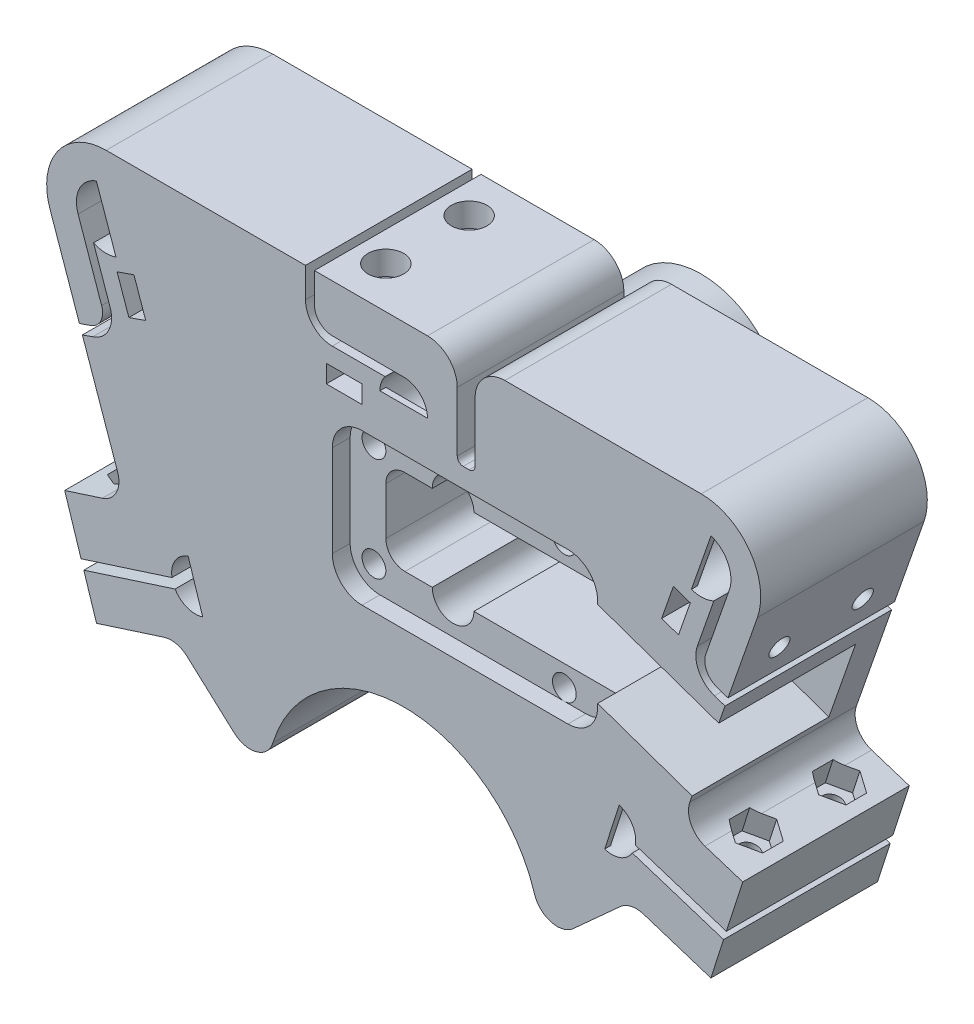
SolidWorks part; units mm, degrees
other "Uwaga1"
sketch "Szkic11" plane through (60, 10, 0) normal (0.4049, 0.0419, -0.9134) x (0.8662, -0.3375, 0.3685)
other "Uwaga2"
sketch "Szkic12" plane through (60, 10, 0) normal (0.4049, 0.0419, -0.9134) x (0.8662, -0.3375, 0.3685)
other "Uwaga3"
sketch "Szkic13"
other "Uwaga4"
sketch "Szkic23" plane through (60, 10, 28) normal (0.2859, 0.0316, 0.9577) x (0.9579, -0.038, -0.2847)
ref_plane "Płaszczyzna przednia" through (0, 0, 0) normal (0, 0, 1) x (1, 0, 0)
ref_plane "Płaszczyzna górna" through (0, 0, 0) normal (0, 1, 0) x (1, 0, 0)
ref_plane "Płaszczyzna prawa" through (0, 0, 0) normal (1, 0, 0) x (0, 0, -1)
sketch "Szkic1" plane through (0, 0, 0) normal (0, 0, 1) x (1, 0, 0)
  line L0 (-50, 10) -> (4, 10)
  line L1 (-59.4412, -3.296) -> (-43.4971, -48.9664)
  line L2 (43.4971, -48.9664) -> (59.4412, -3.296)
  line L3 (-41.0394, -52.6727) -> (-23, -69)
  line L4 (23, -69) -> (41.0394, -52.6727)
  line L5 (38.4257, -48.0651) -> (43.2433, -49.6122)
  line L6 (38.9457, -46.6566) -> (43.7633, -48.2037)
  line L7 (0, -34.7604) -> (35, -46) construction
  line L8 (38.1168, -55.318) -> (51.621, -59.6546)
  line L9 (51.621, -59.6546) -> (53.7613, -52.9898)
  line L10 (53.7613, -52.9898) -> (43.2433, -49.6122)
  line L11 (43.7633, -48.2037) -> (54.2199, -51.5616)
  line L12 (54.2199, -51.5616) -> (56.9717, -42.9926)
  line L13 (56.9717, -42.9926) -> (46.7307, -39.704)
  line L14 (0, -29) -> (0, -114.3862) construction
  line L15 (0, 2) -> (-12, 2)
  line L16 (-3.1225, 0.5) -> (-12, 0.5)
  line L17 (-16.5, 5) -> (-16.5, 10)
  line L18 (-15, 5) -> (-15, 10)
  line L19 (9, 5) -> (9, -5)
  line L20 (10, -6) -> (11, -6)
  line L21 (12, -5) -> (12, 5)
  line L22 (17, 10) -> (50, 10)
  line L23 (-56.9717, -42.9926) -> (-46.7307, -39.704)
  line L24 (-54.2199, -51.5616) -> (-56.9717, -42.9926)
  line L25 (-43.7633, -48.2037) -> (-54.2199, -51.5616)
  line L26 (-38.9457, -46.6566) -> (-43.7633, -48.2037)
  line L27 (-38.4257, -48.0651) -> (-43.2433, -49.6122)
  line L28 (-53.7613, -52.9898) -> (-43.2433, -49.6122)
  line L29 (-51.621, -59.6546) -> (-53.7613, -52.9898)
  line L30 (-38.1168, -55.318) -> (-51.621, -59.6546)
  line L31 (-54.7206, -1.648) -> (-50.7653, -12.9775)
  line L32 (-52.1248, -4.5261) -> (-49.3471, -12.4823)
  line L33 (-52.6089, -16.7986) -> (-54.4971, -17.4578)
  line L34 (-52.2456, -18.2606) -> (-54.0027, -18.874)
  line L35 (54.7206, -1.648) -> (50.7653, -12.9775)
  line L36 (52.1248, -4.5261) -> (49.3471, -12.4823)
  line L37 (52.6089, -16.7986) -> (54.4971, -17.4578)
  line L38 (52.2456, -18.2606) -> (54.0027, -18.874)
  circle A0 centre (-50, 0) radius 5
  circle A1 centre (50, 0) radius 5
  circle A2 centre (-50, 0) radius 10
  circle A3 centre (50, 0) radius 10
  circle A4 centre (0, -2) radius 4
  circle A5 centre (0, -29) radius 15.5 construction
  circle A6 centre (0, -22) radius 4
  circle A13 centre (-35, -46) radius 4
  circle A14 centre (35, -46) radius 4
  circle A15 centre (-35, -46) radius 9
  circle A16 centre (35, -46) radius 9
  arc A17 (23, -69) -> (-23, -69) centre (0, -69) ccw
  arc A19 (-12, 2) -> (-15, 5) centre (-12, 5) cw
  arc A20 (-12, 0.5) -> (-16.5, 5) centre (-12, 5) cw
  arc A21 (9, 5) -> (4, 10) centre (4, 5) ccw
  arc A22 (12, 5) -> (17, 10) centre (17, 5) cw
  arc A23 (11, -6) -> (12, -5) centre (11, -5) ccw
  arc A24 (9, -5) -> (10, -6) centre (10, -5) ccw
  arc A25 (-50.7653, -12.9775) -> (-52.6089, -16.7986) centre (-53.5977, -13.9663) cw
  arc A26 (-49.3471, -12.4823) -> (-52.2456, -18.2606) centre (-53.5977, -13.9663) cw
  arc A27 (49.3471, -12.4823) -> (52.2456, -18.2606) centre (53.5977, -13.9663) ccw
  arc A28 (50.7653, -12.9775) -> (52.6089, -16.7986) centre (53.5977, -13.9663) ccw
  point P32 (0, -29)
  point P78 (10.1421, 10)
  point P84 (10.1421, -2)
  point P87 (7.1421, -2)
  point P103 (-49.7765, -15.8098)
  dimension "D1" = 10
  dimension "D6" = 8
  dimension "D8" = 31
  dimension "D9" = 8
  dimension "D14" = 70
  dimension "D18" = 46
  dimension "D27" = 3
  dimension "D28" = 4.5
  dimension "D31" = 5
  dimension "D32" = 5
  dimension "D33" = 1
  dimension "D38" = 3
  dimension "D39" = 12.7604
  dimension "D2" = 100
  dimension "D3" = 50
  dimension "D7" = 39
  dimension "D10" = 7
  dimension "D11" = 12
  dimension "D15" = 35
  dimension "D16" = 46
  dimension "D19" = 40
  dimension "D20" = 1.5
  dimension "D21" = 7
  dimension "D22" = 20
  dimension "D23" = 9
  dimension "D24" = 1.5
  dimension "D25" = 1.5
  dimension "D26" = 15
  dimension "D29" = 3
  dimension "D30" = 16
  dimension "D34" = 9
  dimension "D35" = 15
  dimension "D36" = 1.5021
  dimension "D37" = 1.5
  dimension "D4" = 5
  dimension "D5" = 5
  dimension "D17" = 5
extrude "Dodanie-wyciągnięcie1" add sketch "Szkic1" along normal blind 28 contours A2 A0 | A17 L4 A16 L2 A3 L0 A2 L1 A15 L3 A6 A4 | A3 A1 | A16 A14 | A15 A13 | A16 L4 L8 L9 L10 | L12 L13 L2 L11 | A15 L28 L29 L30 L3 | L25 L1 L23 L24 | A25 L31 A2 L1 L33 | L35 A28 L37 L2 A3 region at (-33.25, 8.6619, 0) region at (-43.1289, 6.8711, 0) region at (-54.1165, -12.2056, 0) region at (-50.4165, -45.6303, 0) region at (-36.0734, -37.3207, 0) region at (-46.741, -54.5771, 0) region at (56.8711, 6.8711, 0) region at (46.741, -54.5771, 0) region at (54.1165, -12.2056, 0) region at (27.0061, -42.4532, 0) region at (50.4165, -45.6303, 0)
fillet "Zaokrąglenie1" radius 4 6 edges at (-46.7307, -39.704, 14) (-38.1168, -55.318, 14) (-23, -69, 14) (23, -69, 14) (38.1168, -55.318, 14) (46.7307, -39.704, 14)
sketch "Szkic2" plane through (12.5403, -39.0504, 0) normal (0.3058, -0.9521, 0) x (0.9521, 0.3058, 0)
  line L0 (-55.5122, 28) -> (-67.3885, 28) construction
  line L1 (-67.3885, 28) -> (-67.3885, 0) construction
  circle A0 centre (-62.3885, 21) radius 1.7
  circle A1 centre (-62.3885, 7) radius 1.7
  dimension "D1" = 14
  dimension "D4" = 3.4
  dimension "D2" = 7
  dimension "D3" = 5
extrude "Wytnij-wyciągnięcie1" cut sketch "Szkic2" against normal through all
sketch "Szkic3" plane through (12.5403, -39.0504, 0) normal (0.3058, -0.9521, 0) x (0.9521, 0.3058, 0)
  circle A0 centre (-62.3885, 21) radius 3
  circle A1 centre (-62.3885, 7) radius 3
  dimension "D1" = 6
extrude "Wytnij-wyciągnięcie2" cut sketch "Szkic3" against normal blind 3
sketch "Szkic4" plane through (7.1896, -22.3885, 0) normal (-0.3058, 0.9521, 0) x (0.9521, 0.3058, 0)
  line L1 (-62.3885, -24.4641) -> (-59.3885, -22.7321)
  line L2 (-59.3885, -22.7321) -> (-59.3885, -19.2679)
  line L3 (-59.3885, -19.2679) -> (-62.3885, -17.5359)
  line L4 (-62.3885, -17.5359) -> (-65.3885, -19.2679)
  line L5 (-65.3885, -19.2679) -> (-65.3885, -22.7321)
  line L6 (-65.3885, -22.7321) -> (-62.3885, -24.4641)
  line L7 (-62.3885, -10.4641) -> (-59.3885, -8.7321)
  line L8 (-59.3885, -8.7321) -> (-59.3885, -5.2679)
  line L9 (-59.3885, -5.2679) -> (-62.3885, -3.5359)
  line L10 (-62.3885, -3.5359) -> (-65.3885, -5.2679)
  line L11 (-65.3885, -5.2679) -> (-65.3885, -8.7321)
  line L12 (-65.3885, -8.7321) -> (-62.3885, -10.4641)
  circle A0 centre (-62.3885, -21) radius 3 construction
  circle A1 centre (-62.3885, -7) radius 3 construction
  dimension "D1" = 6
extrude "Wytnij-wyciągnięcie3" cut sketch "Szkic4" against normal blind 4 and the other way blind 4
sketch "Szkic5" plane through (-54.0092, -18.8553, 0) normal (-0.9441, -0.3296, 0) x (0, 0, 1)
  line L0 (28, 16.4802) -> (28, 1.4802) construction
  line L1 (28, 1.4802) -> (0, 1.4802) construction
  circle A0 centre (21, 6.4802) radius 1.7
  circle A1 centre (7, 6.4802) radius 1.7
  dimension "D1" = 14
  dimension "D2" = 3.4
  dimension "D3" = 7
  dimension "D4" = 5
extrude "Wytnij-wyciągnięcie4" cut sketch "Szkic5" against normal blind 10
sketch "Szkic6" plane through (-54.0092, -18.8553, 0) normal (-0.9441, -0.3296, 0) x (0, 0, 1)
  line L0 (22.7321, 9.4802) -> (28, 9.4802)
  line L1 (24.4641, 6.4802) -> (22.7321, 9.4802)
  line L2 (22.7321, 9.4802) -> (19.2679, 9.4802)
  line L3 (19.2679, 9.4802) -> (17.5359, 6.4802)
  line L4 (17.5359, 6.4802) -> (19.2679, 3.4802)
  line L5 (19.2679, 3.4802) -> (22.7321, 3.4802)
  line L6 (22.7321, 3.4802) -> (24.4641, 6.4802)
  line L7 (10.4641, 6.4802) -> (8.7321, 9.4802)
  line L8 (8.7321, 9.4802) -> (5.2679, 9.4802)
  line L9 (5.2679, 9.4802) -> (3.5359, 6.4802)
  line L10 (3.5359, 6.4802) -> (5.2679, 3.4802)
  line L11 (5.2679, 3.4802) -> (8.7321, 3.4802)
  line L12 (8.7321, 3.4802) -> (10.4641, 6.4802)
  line L13 (28, 16.4802) -> (28, 1.4802) construction
  line L14 (28, 9.4802) -> (28, 3.4802)
  line L15 (28, 3.4802) -> (22.7321, 3.4802)
  line L16 (5.2679, 9.4802) -> (0, 9.4802)
  line L17 (0, 16.4802) -> (0, 1.4802) construction
  line L18 (0, 9.4802) -> (0, 3.4802)
  line L19 (0, 3.4802) -> (5.2679, 3.4802)
  circle A0 centre (21, 6.4802) radius 3 construction
  circle A1 centre (7, 6.4802) radius 3 construction
  circle M2 centre (21, 6.4802) radius 1.7
  circle M3 centre (7, 6.4802) radius 1.7
  line M4 (0, 16.4802) -> (0, 1.4802)
  line M6 (28, 1.4802) -> (28, 16.4802)
  dimension "D1" = 6
extrude "Wytnij-wyciągnięcie5" cut sketch "Szkic6" against normal blind 3 from offset 9.5 contours L5 L6 L1 L2 L3 L4 M2 | L15 L0 L1 L6 M6 | L19 L10 L9 L16 M4 | L11 L12 L7 L8 L9 L10 M3 | M2 | M3 region at (-56.1452, -12.7372, 25.7706) region at (-56.6245, -11.3643, 23.5187) region at (-55.6658, -14.1101, 9.5187) region at (-56.1452, -12.7372, 2.2294) region at (-56.1452, -12.7372, 21) region at (-56.1452, -12.7372, 7) offset against normal yes
mirror "Lustro1" about plane through (0, 0, 0) normal (1, 0, 0) of "Wytnij-wyciągnięcie5", "Wytnij-wyciągnięcie4", "Wytnij-wyciągnięcie2", "Wytnij-wyciągnięcie1", "Wytnij-wyciągnięcie3"
sketch "Szkic7" plane through (0, 10, 0) normal (0, 1, 0) x (1, 0, 0)
  line L0 (-15, 0) -> (4, 0) construction
  line L1 (-15, -28) -> (-15, 0) construction
  circle A0 centre (-10, -21) radius 1.7
  circle A1 centre (-10, -7) radius 1.7
  dimension "D1" = 3.4
  dimension "D2" = 14
  dimension "D3" = 7
  dimension "D4" = 5
extrude "Wytnij-wyciągnięcie6" cut sketch "Szkic7" against normal blind 14
sketch "Szkic8" plane through (0, 10, 0) normal (0, 1, 0) x (1, 0, 0)
  line L0 (-7, -22.7321) -> (-7, -28)
  line L1 (-10, -24.4641) -> (-7, -22.7321)
  line L2 (-7, -22.7321) -> (-7, -19.2679)
  line L3 (-7, -19.2679) -> (-10, -17.5359)
  line L4 (-10, -17.5359) -> (-13, -19.2679)
  line L5 (-13, -19.2679) -> (-13, -22.7321)
  line L6 (-13, -22.7321) -> (-10, -24.4641)
  line L7 (-10, -10.4641) -> (-7, -8.7321)
  line L8 (-7, -8.7321) -> (-7, -5.2679)
  line L9 (-7, -5.2679) -> (-10, -3.5359)
  line L10 (-10, -3.5359) -> (-13, -5.2679)
  line L11 (-13, -5.2679) -> (-13, -8.7321)
  line L12 (-13, -8.7321) -> (-10, -10.4641)
  line L13 (-15, -28) -> (4, -28) construction
  line L14 (-7, -28) -> (-13, -28)
  line L15 (-13, -28) -> (-13, -22.7321)
  line L16 (-7, -5.2679) -> (-7, 0)
  line L17 (-15, 0) -> (4, 0) construction
  line L18 (-7, 0) -> (-13, 0)
  line L19 (-13, 0) -> (-13, -5.2679)
  circle A0 centre (-10, -21) radius 3 construction
  circle A1 centre (-10, -7) radius 3 construction
  circle M1 centre (-10, -21) radius 1.7
  circle M2 centre (-10, -7) radius 1.7
  line M3 (4, 0) -> (-15, 0)
  line M5 (-15, -28) -> (4, -28)
  dimension "D1" = 6
extrude "Wytnij-wyciągnięcie7" cut sketch "Szkic8" against normal blind 3 from offset 12.5 contours L5 L6 L1 L2 L3 L4 M1 | M1 | L15 L0 L1 L6 M5 | M2 | L11 L12 L7 L8 L9 L10 M2 | L19 L10 L9 L16 M3 region at (-10, 10, 25.7706) region at (-8.5458, 10, 23.5187) region at (-11.4542, 10, 9.5187) region at (-10, 10, 2.2294) region at (-10, 10, 21) region at (-10, 10, 7) offset against normal yes
sketch "Szkic9" plane through (0, 0, 28) normal (0, 0, 1) x (1, 0, 0)
  line L0 (-36.223, -42.1916) -> (-33.777, -49.8084)
  line L1 (36.223, -42.1916) -> (33.777, -49.8084)
  line L2 (-51.648, 4.7206) -> (-48.352, -4.7206)
  line L3 (51.648, 4.7206) -> (48.352, -4.7206)
  line L4 (-4, -2) -> (4, -2)
  line L36 (-36.4063, -56.8662) -> (-28.4915, -64.0297)
  line L37 (28.4915, -64.0297) -> (36.4063, -56.8662)
  line L38 (40.3135, -56.0234) -> (51.621, -59.6546)
  line L39 (51.621, -59.6546) -> (53.7613, -52.9898)
  line L40 (53.7613, -52.9898) -> (38.4257, -48.0651)
  line L41 (38.9457, -46.6566) -> (54.2199, -51.5616)
  line L42 (54.2199, -51.5616) -> (56.9717, -42.9926)
  line L43 (56.9717, -42.9926) -> (50.6362, -40.9581)
  line L44 (48.0827, -35.8313) -> (54.0027, -18.874)
  line L45 (54.0027, -18.874) -> (52.2456, -18.2606)
  line L46 (49.3471, -12.4823) -> (52.1248, -4.5261)
  line L47 (54.7206, -1.648) -> (50.7653, -12.9775)
  line L48 (52.6089, -16.7986) -> (54.4971, -17.4578)
  line L49 (54.4971, -17.4578) -> (59.4412, -3.296)
  line L50 (50, 10) -> (17, 10)
  line L51 (12, 5) -> (12, -5)
  line L52 (11, -6) -> (10, -6)
  line L53 (9, -5) -> (9, 5)
  line L54 (4, 10) -> (-15, 10)
  line L55 (-15, 10) -> (-15, 5)
  line L56 (-12, 2) -> (0, 2)
  line L57 (-3.1225, 0.5) -> (-12, 0.5)
  line L58 (-16.5, 5) -> (-16.5, 10)
  line L59 (-16.5, 10) -> (-50, 10)
  line L60 (-59.4412, -3.296) -> (-54.4971, -17.4578)
  line L61 (-54.4971, -17.4578) -> (-52.6089, -16.7986)
  line L62 (-50.7653, -12.9775) -> (-54.7206, -1.648)
  line L63 (-52.1248, -4.5261) -> (-49.3471, -12.4823)
  line L64 (-52.2456, -18.2606) -> (-54.0027, -18.874)
  line L65 (-54.0027, -18.874) -> (-48.0827, -35.8313)
  line L66 (-50.6362, -40.9581) -> (-56.9717, -42.9926)
  line L67 (-56.9717, -42.9926) -> (-54.2199, -51.5616)
  line L68 (-54.2199, -51.5616) -> (-38.9457, -46.6566)
  line L69 (-38.4257, -48.0651) -> (-53.7613, -52.9898)
  line L70 (-53.7613, -52.9898) -> (-51.621, -59.6546)
  line L71 (-51.621, -59.6546) -> (-40.3135, -56.0234)
  line L72 (-36.4063, -56.8662) -> (-28.4915, -64.0297)
  line L73 (28.4915, -64.0297) -> (36.4063, -56.8662)
  line L74 (40.3135, -56.0234) -> (51.621, -59.6546)
  line L75 (51.621, -59.6546) -> (53.7613, -52.9898)
  line L76 (53.7613, -52.9898) -> (38.4257, -48.0651)
  line L77 (38.9457, -46.6566) -> (54.2199, -51.5616)
  line L78 (54.2199, -51.5616) -> (56.9717, -42.9926)
  line L79 (56.9717, -42.9926) -> (50.6362, -40.9581)
  line L80 (48.0827, -35.8313) -> (54.0027, -18.874)
  line L81 (54.0027, -18.874) -> (52.2456, -18.2606)
  line L82 (49.3471, -12.4823) -> (52.1248, -4.5261)
  line L83 (54.7206, -1.648) -> (50.7653, -12.9775)
  line L84 (52.6089, -16.7986) -> (54.4971, -17.4578)
  line L85 (54.4971, -17.4578) -> (59.4412, -3.296)
  line L86 (50, 10) -> (17, 10)
  line L87 (12, 5) -> (12, -5)
  line L88 (11, -6) -> (10, -6)
  line L89 (9, -5) -> (9, 5)
  line L90 (4, 10) -> (-15, 10)
  line L91 (-15, 10) -> (-15, 5)
  line L92 (-12, 2) -> (0, 2)
  line L93 (-3.1225, 0.5) -> (-12, 0.5)
  line L94 (-16.5, 5) -> (-16.5, 10)
  line L95 (-16.5, 10) -> (-50, 10)
  line L96 (-59.4412, -3.296) -> (-54.4971, -17.4578)
  line L97 (-54.4971, -17.4578) -> (-52.6089, -16.7986)
  line L98 (-50.7653, -12.9775) -> (-54.7206, -1.648)
  line L99 (-52.1248, -4.5261) -> (-49.3471, -12.4823)
  line L100 (-52.2456, -18.2606) -> (-54.0027, -18.874)
  line L101 (-54.0027, -18.874) -> (-48.0827, -35.8313)
  line L102 (-50.6362, -40.9581) -> (-56.9717, -42.9926)
  line L103 (-56.9717, -42.9926) -> (-54.2199, -51.5616)
  line L104 (-54.2199, -51.5616) -> (-38.9457, -46.6566)
  line L105 (-38.4257, -48.0651) -> (-53.7613, -52.9898)
  line L106 (-53.7613, -52.9898) -> (-51.621, -59.6546)
  line L107 (-51.621, -59.6546) -> (-40.3135, -56.0234)
  arc A24 (-28.4915, -64.0297) -> (-21.984, -62.2397) centre (-25.8074, -61.064) ccw
  arc A25 (21.984, -62.2397) -> (-21.984, -62.2397) centre (0, -69) ccw
  arc A26 (21.984, -62.2397) -> (28.4915, -64.0297) centre (25.8074, -61.064) ccw
  arc A27 (40.3135, -56.0234) -> (36.4063, -56.8662) centre (39.0904, -59.8318) ccw
  arc A28 (38.9457, -46.6566) -> (38.4257, -48.0651) centre (35, -46) ccw
  arc A29 (48.0827, -35.8313) -> (50.6362, -40.9581) centre (51.8592, -37.1497) ccw
  arc A30 (49.3471, -12.4823) -> (52.2456, -18.2606) centre (53.5977, -13.9663) ccw
  arc A31 (54.7206, -1.648) -> (52.1248, -4.5261) centre (50, 0) ccw
  arc A32 (50.7653, -12.9775) -> (52.6089, -16.7986) centre (53.5977, -13.9663) ccw
  arc A33 (59.4412, -3.296) -> (50, 10) centre (50, 0) ccw
  arc A34 (17, 10) -> (12, 5) centre (17, 5) ccw
  arc A35 (11, -6) -> (12, -5) centre (11, -5) ccw
  arc A36 (9, -5) -> (10, -6) centre (10, -5) ccw
  arc A37 (9, 5) -> (4, 10) centre (4, 5) ccw
  arc A38 (-15, 5) -> (-12, 2) centre (-12, 5) ccw
  arc A39 (-3.1225, 0.5) -> (0, 2) centre (0, -2) ccw
  arc A40 (-16.5, 5) -> (-12, 0.5) centre (-12, 5) ccw
  arc A41 (-50, 10) -> (-59.4412, -3.296) centre (-50, 0) ccw
  arc A42 (-52.6089, -16.7986) -> (-50.7653, -12.9775) centre (-53.5977, -13.9663) ccw
  arc A43 (-52.1248, -4.5261) -> (-54.7206, -1.648) centre (-50, 0) ccw
  arc A44 (-52.2456, -18.2606) -> (-49.3471, -12.4823) centre (-53.5977, -13.9663) ccw
  arc A45 (-50.6362, -40.9581) -> (-48.0827, -35.8313) centre (-51.8592, -37.1497) ccw
  arc A46 (-38.4257, -48.0651) -> (-38.9457, -46.6566) centre (-35, -46) ccw
  arc A47 (-36.4063, -56.8662) -> (-40.3135, -56.0234) centre (-39.0904, -59.8318) ccw
  arc A48 (-28.4915, -64.0297) -> (-21.984, -62.2397) centre (-25.8074, -61.064) ccw
  arc A49 (21.984, -62.2397) -> (-21.984, -62.2397) centre (0, -69) ccw
  arc A50 (21.984, -62.2397) -> (28.4915, -64.0297) centre (25.8074, -61.064) ccw
  arc A51 (40.3135, -56.0234) -> (36.4063, -56.8662) centre (39.0904, -59.8318) ccw
  arc A52 (38.9457, -46.6566) -> (38.4257, -48.0651) centre (35, -46) ccw
  arc A53 (48.0827, -35.8313) -> (50.6362, -40.9581) centre (51.8592, -37.1497) ccw
  arc A54 (49.3471, -12.4823) -> (52.2456, -18.2606) centre (53.5977, -13.9663) ccw
  arc A55 (54.7206, -1.648) -> (52.1248, -4.5261) centre (50, 0) ccw
  arc A56 (50.7653, -12.9775) -> (52.6089, -16.7986) centre (53.5977, -13.9663) ccw
  arc A57 (59.4412, -3.296) -> (50, 10) centre (50, 0) ccw
  arc A58 (17, 10) -> (12, 5) centre (17, 5) ccw
  arc A59 (11, -6) -> (12, -5) centre (11, -5) ccw
  arc A60 (9, -5) -> (10, -6) centre (10, -5) ccw
  arc A61 (9, 5) -> (4, 10) centre (4, 5) ccw
  arc A62 (-15, 5) -> (-12, 2) centre (-12, 5) ccw
  arc A63 (-3.1225, 0.5) -> (0, 2) centre (0, -2) ccw
  arc A64 (-16.5, 5) -> (-12, 0.5) centre (-12, 5) ccw
  arc A65 (-50, 10) -> (-59.4412, -3.296) centre (-50, 0) ccw
  arc A66 (-52.6089, -16.7986) -> (-50.7653, -12.9775) centre (-53.5977, -13.9663) ccw
  arc A67 (-52.1248, -4.5261) -> (-54.7206, -1.648) centre (-50, 0) ccw
  arc A68 (-52.2456, -18.2606) -> (-49.3471, -12.4823) centre (-53.5977, -13.9663) ccw
  arc A69 (-50.6362, -40.9581) -> (-48.0827, -35.8313) centre (-51.8592, -37.1497) ccw
  arc A70 (-38.4257, -48.0651) -> (-38.9457, -46.6566) centre (-35, -46) ccw
  arc A71 (-36.4063, -56.8662) -> (-40.3135, -56.0234) centre (-39.0904, -59.8318) ccw
  dimension "D1" = 0
extrude "Dodanie-wyciągnięcie2" add sketch "Szkic9" against normal blind 1 contours L2 A67 | L4 A63 | L3 A55 | L1 A52 | L0 A70 region at (-33.3836, -45.4809, 28) region at (-47.9965, 0.6994, 28) region at (33.3836, -45.4809, 28) region at (0, -3.6977, 28) region at (47.9965, 0.6994, 28)
sketch "Szkic14" plane through (0, 10, 0) normal (0, 1, 0) x (1, 0, 0)
  circle A0 centre (-10, -7) radius 3
  circle A1 centre (-10, -21) radius 3
  dimension "D1" = 6
extrude "Wytnij-wyciągnięcie9" cut sketch "Szkic14" against normal blind 4
sketch "Szkic15" plane through (0, 0, 28) normal (0, 0, 1) x (1, 0, 0)
  line L0 (-6, -26) -> (-6, -18)
  line L1 (-2.8, -29.2) -> (1.8, -29.2)
  line L2 (-2.8, -14.8) -> (1.8, -14.8)
  line L3 (8.8, -29.2) -> (22.6, -29.2)
  line L4 (22.6, -29.2) -> (22.6, -14.8)
  line L5 (22.6, -14.8) -> (8.8, -14.8)
  line L6 (22.6, -14.8) -> (32.6, -14.8)
  line L7 (32.6, -14.8) -> (32.6, -29.2)
  line L8 (32.6, -29.2) -> (22.6, -29.2)
  line L9 (32.6, -14.8) -> (52.9453, -21.9028)
  line L10 (48.0827, -35.8313) -> (54.0027, -18.874) construction
  line L11 (32.6, -29.2) -> (48.4643, -34.7384)
  line L12 (52.9453, -21.9028) -> (48.4643, -34.7384)
  circle A1 centre (0, -22) radius 4
  arc A2 (-6, -18) -> (-2.8, -14.8) centre (-2.8, -18) cw
  arc A3 (-6, -26) -> (-2.8, -29.2) centre (-2.8, -26) ccw
  arc A6 (1.8, -29.2) -> (8.8, -29.2) centre (5.3, -29.2) ccw
  circle A7 centre (0, -22) radius 4 construction
  circle A8 centre (0, -22) radius 4
  arc A9 (8.8, -14.8) -> (1.8, -14.8) centre (5.3, -14.8) ccw
  dimension "D2" = 3.2
  dimension "D5" = 7
  dimension "D7" = 28.6
  dimension "D8" = 10
  dimension "D1" = 6
  dimension "D3" = 14.4
  dimension "D4" = 7.2
  dimension "D6" = 11.3
extrude "Wytnij-wyciągnięcie10" cut sketch "Szkic15" against normal blind 23 contours L5 A9 L2 A2 L0 A3 L1 A6 L3 L4 A1 | L8 L7 L6 L4 | L12 L9 L7 L11 region at (9.2135, -22, 28) region at (27.6, -22, 28) region at (41.6986, -24.8794, 28)
sketch "Szkic16" plane through (0, 0, 28) normal (0, 0, 1) x (1, 0, 0)
  line L0 (-6, -26) -> (-6, -18) construction
  line L1 (-7, -9.3) -> (27.6, -9.3)
  line L2 (-12, -14.3) -> (-12, -29.7)
  line L3 (-7, -34.7) -> (27.6, -34.7)
  line L4 (32.6, -14.3) -> (32.6, -29.7)
  line L5 (32.6, -14.8) -> (8.8, -14.8) construction
  line L7 (8.8, -29.2) -> (32.6, -29.2) construction
  arc A0 (27.6, -9.3) -> (32.6, -14.3) centre (27.6, -14.3) cw
  arc A1 (27.6, -34.7) -> (32.6, -29.7) centre (27.6, -29.7) ccw
  arc A2 (-12, -29.7) -> (-7, -34.7) centre (-7, -29.7) ccw
  arc A3 (-7, -9.3) -> (-12, -14.3) centre (-7, -14.3) ccw
  dimension "D2" = 5
  dimension "D1" = 5.5
  dimension "D3" = 6
  dimension "D4" = 5.5
extrude "Wytnij-wyciągnięcie11" cut sketch "Szkic16" against normal blind 3
sketch "Szkic17" plane through (0, 0, 25) normal (0, 0, 1) x (1, 0, 0)
  line L0 (-12, -14.3) -> (-12, -29.7) construction
  line L1 (27.6, -9.3) -> (-7, -9.3) construction
  line L2 (-7, -34.7) -> (27.6, -34.7) construction
  circle A0 centre (-8, -13.3) radius 2
  circle A1 centre (-8, -30.7) radius 2
  circle A2 centre (24, -32.7) radius 2
  circle A3 centre (24, -11.3) radius 2
  dimension "D1" = 4
  dimension "D2" = 4
  dimension "D3" = 4
  dimension "D4" = 4
  dimension "D5" = 2
  dimension "D6" = 2
  dimension "D7" = 32
extrude "Wytnij-wyciągnięcie12" cut sketch "Szkic17" against normal blind 6
sketch "Szkic18" plane through (0, 0, 5) normal (0, 0, 1) x (1, 0, 0)
  circle A0 centre (5.3, -14.8) radius 2
  circle A1 centre (5.3, -29.2) radius 2
  dimension "D1" = 4
extrude "Wytnij-wyciągnięcie13" cut sketch "Szkic18" against normal blind 4
sketch "Szkic19" plane through (0, 0, 5) normal (0, 0, 1) x (1, 0, 0)
  line L1 (8.8, -18) -> (21.8, -18)
  line L2 (8.8, -18) -> (8.8, -26)
  line L3 (8.8, -26) -> (21.8, -26)
  line L4 (21.8, -18) -> (21.8, -26)
  circle A0 centre (0, -22) radius 4 construction
  circle A1 centre (0, -22) radius 4
  point P8 (8.8, -22)
  dimension "D1" = 8
  dimension "D2" = 13
  dimension "D3" = 8.8
extrude "Wytnij-wyciągnięcie14" cut sketch "Szkic19" against normal blind 4
sketch "Szkic20" plane through (0, 0, 0) normal (0, 0, -1) x (-1, 0, 0)
  circle A0 centre (0, -22) radius 4 construction
  circle A1 centre (0, -22) radius 4
  circle A2 centre (0, -22) radius 14
  dimension "D1" = 28
extrude "Dodanie-wyciągnięcie3" add sketch "Szkic20" along normal blind 22
sketch "Szkic21" plane through (0, 0, -22) normal (0, 0, -1) x (-1, 0, 0)
  circle A0 centre (0, -22) radius 4 construction
  circle A1 centre (0, -22) radius 4
  circle A2 centre (0, -22) radius 14 construction
  circle A3 centre (0, -22) radius 14
  circle A4 centre (0, -22) radius 11.05
  circle M2 centre (0, -22) radius 4
  dimension "D1" = 22.1
extrude "Wytnij-wyciągnięcie15" cut sketch "Szkic21" against normal blind 7 contours A4 M2 region at (10.7375, -22, -22)
sketch "Szkic22" plane through (0, 0, -15) normal (0, 0, -1) x (-1, 0, 0)
  circle A0 centre (0, -22) radius 8
  circle A1 centre (0, -22) radius 4 construction
  circle A2 centre (0, -22) radius 4
  dimension "D1" = 16
extrude "Wytnij-wyciągnięcie16" cut sketch "Szkic22" against normal blind 15
chamfer "Sfazowanie1" distance 2 angle 45 1 edges at (14, -22, 0)
chamfer "Sfazowanie2" distance 5 angle 45 1 edges at (0, -46, 0) tangent propagation no
chamfer "Sfazowanie3" distance 0.5 distance2 12 1 edges at (-8, -22, -15) first distance on face at (-8, -22, -15)
